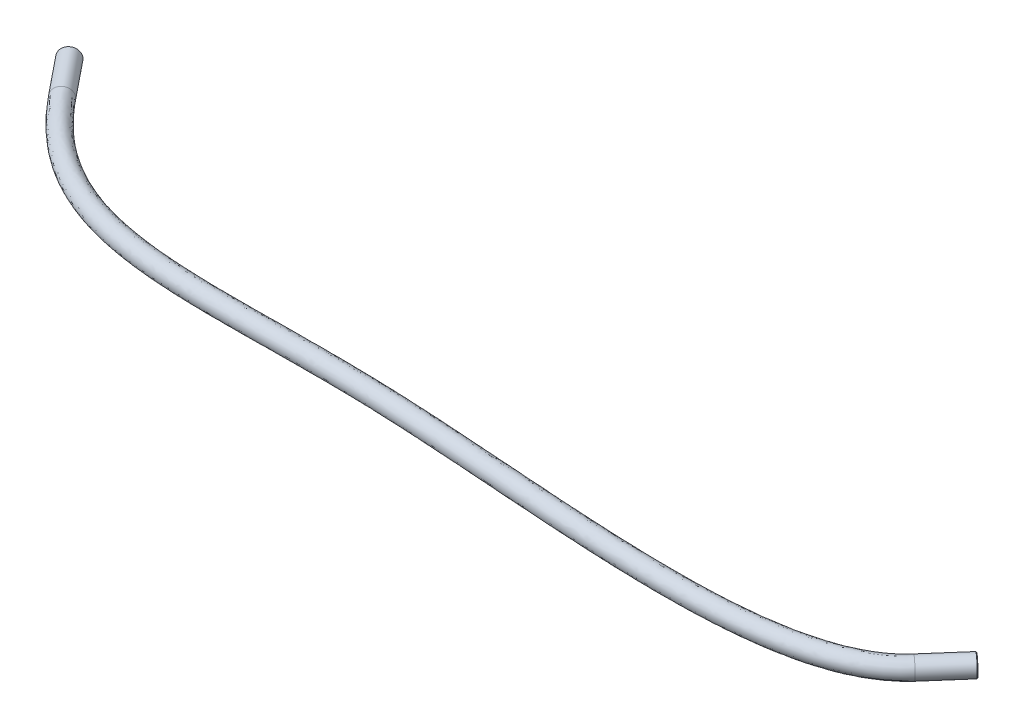
SolidWorks part; units mm, degrees
ref_plane "Front Plane" through (0, 0, 0) normal (0, 0, 1) x (1, 0, 0)
ref_plane "Top Plane" through (0, 0, 0) normal (0, 1, 0) x (1, 0, 0)
ref_plane "Right Plane" through (0, 0, 0) normal (1, 0, 0) x (0, 0, -1)
sketch3d "3DSketch1"
  line L0 (43.1041, -99.6875, 35.7814) -> (49.1644, -99.6875, 28.8595)
  line L1 (-152.9482, -99.5875, 13.9938) -> (-146.5343, -99.5875, 21.9249)
  spline S0 degree 3 poles (-146.5343, -99.5875, 21.9249) (-125.2413, -99.5875, 48.2549) (-75.3701, -99.6375, 35.0332) (28.3692, -99.6875, 52.6113) (43.1041, -99.6875, 35.7814) knots 0 0 0 0 0.504003 1 1 1 1
sketch "Sketch1" plane through (2.3534, 0, -2.688) normal (-0.6587, 0, 0.7524) x (0.7524, 0, 0.6587)
  circle A0 centre (56.001, -99.6875) radius 2
  circle A1 centre (56.001, -99.6875) radius 1.3
  circle A3 centre (56.001, -99.6875) radius 3.5524 construction
  dimension "D1" = 2.6
  dimension "D2" = 4
sweep "Sweep2" add profiles "Sketch1" path "3DSketch1"
chamfer "Chamfer1" distance 0.127 angle 45 4 edges at (-154.5033, -99.5863, 15.2514) (-153.959, -99.5867, 14.8113) (50.6692, -99.6875, 30.177) (50.1425, -99.6875, 29.7159)
